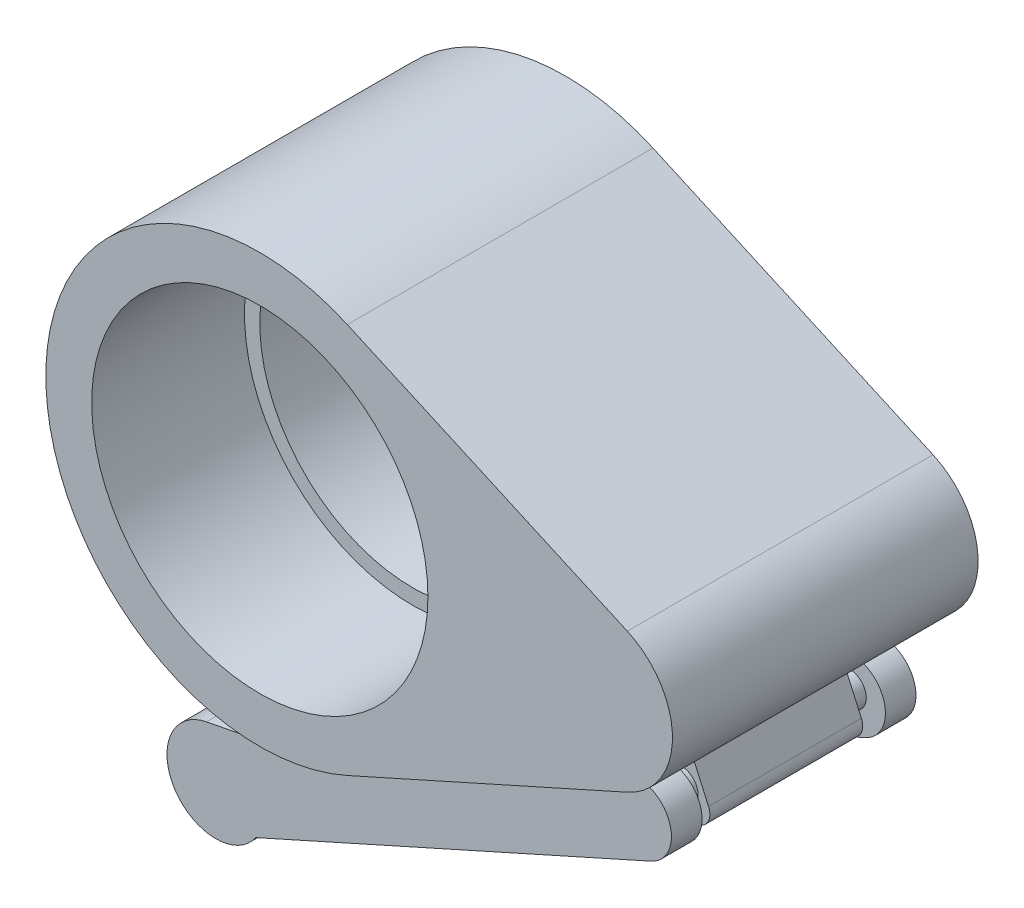
SolidWorks part; units mm, degrees
material "BUTYL"
ref_plane "Plan de face" through (0, 0, 0) normal (0, 0, 1) x (1, 0, 0)
ref_plane "Plan de dessus" through (0, 0, 0) normal (0, 1, 0) x (1, 0, 0)
ref_plane "Plan de droite" through (0, 0, 0) normal (1, 0, 0) x (0, 0, -1)
sketch "Esquisse2" plane through (0, 0, 0) normal (0, 0, 1) x (1, 0, 0)
  line L0 (5.7273, 12.7749) -> (24.0455, 4.5625)
  line L1 (5.7273, -12.7749) -> (24.0455, -4.5625)
  arc A0 (5.7273, 12.7749) -> (5.7273, -12.7749) centre (0, 0) ccw
  arc A1 (24.0455, -4.5625) -> (24.0455, 4.5625) centre (22, 0) ccw
  circle A2 centre (0, 0) radius 10
  dimension "D1" = 14
  dimension "D3" = 5
  dimension "D4" = 20
  dimension "D2" = 22
extrude "Boss.-Extru.1" add sketch "Esquisse2" along normal blind 20
sketch "Esquisse3" plane through (0, 0, 20) normal (0, 0, 1) x (1, 0, 0)
  circle A0 centre (0, 0) radius 11
  circle A1 centre (0, 0) radius 10
  dimension "D1" = 22
  dimension "D2" = 1
extrude "Enlèv. mat.-Extru.1" cut sketch "Esquisse3" against normal blind 10
sketch "Esquisse4" plane through (5.7273, -12.7749, 0) normal (0.4091, -0.9125, 0) x (0.9125, 0.4091, 0)
  line L0 (0, 20) -> (20.0749, 20) construction
  line L1 (16.0749, 15) -> (19.0749, 15)
  line L2 (16.0749, 15) -> (16.0749, 5)
  line L3 (16.0749, 5) -> (19.0749, 5)
  line L4 (19.0749, 15) -> (19.0749, 5)
  line L5 (20.0749, 20) -> (20.0749, 0) construction
  dimension "D1" = 10
  dimension "D2" = 5
  dimension "D3" = 1
  dimension "D4" = 3
extrude "Boss.-Extru.2" add sketch "Esquisse4" along normal blind 4
sketch "Esquisse5" plane through (0, 0, 15) normal (0, 0, 1) x (1, 0, 0)
  line L0 (24.7693, -8.6215) -> (23.133, -4.9716) construction
  line L1 (24.7693, -8.6215) -> (22.0318, -9.8488) construction
  circle A0 centre (22.5824, -7.4102) radius 1.1
  dimension "D3" = 2.2
  dimension "D1" = 1.5
  dimension "D2" = 2
extrude "Boss.-Extru.3" add sketch "Esquisse5" along normal blind 1
sketch "Esquisse6" plane through (7.3636, -16.4249, 0) normal (0.4091, -0.9125, 0) x (0.9125, 0.4091, 0)
  line L0 (16.0749, 10) -> (19.0749, 10) construction
  line L1 (16.0749, 15) -> (16.0749, 5) construction
  line L2 (19.0749, 5) -> (19.0749, 15) construction
ref_plane "Plan1" through (0, 0, 10) normal (0, 0, 1) x (1, 0, 0)
mirror "Symétrie1" about plane through (0, 0, 10) normal (0, 0, 1) of "Boss.-Extru.3"
sketch "Esquisse9" plane through (0, 0, 16) normal (0, 0, 1) x (1, 0, 0)
  line L0 (23.6051, -9.6914) -> (-2.2602, -21.2874)
  line L1 (5.7273, -12.7749) -> (24.0455, -4.5625) construction
  line L2 (-5.4847, -16.3395) -> (-0.9203, -15.4625)
  line L3 (1.2837, -14.767) -> (21.7642, -5.5852)
  line L4 (19.483, -6.6079) -> (21.3239, -10.7141)
  line L5 (22.0318, -9.8488) -> (20.3955, -6.1988) construction
  line L6 (22.5824, -7.4102) -> (23.6622, -9.8186) construction
  arc A0 (-2.2602, -21.2874) -> (-5.4847, -16.3395) centre (-4.8828, -19.4719) cw
  arc A1 (21.7642, -5.5852) -> (23.6051, -9.6914) centre (22.6847, -7.6383) cw
  arc A2 (1.2837, -14.767) -> (-0.9203, -15.4625) centre (-2.8072, -5.6421) cw
  circle M8 centre (22.5824, -7.4102) radius 1.1
  dimension "D1" = 10
  dimension "D2" = 4.5
  dimension "D3" = 30
  dimension "D4" = 1
extrude "Boss.-Extru.5" add sketch "Esquisse9" along normal blind 2 contours A1 L3 L4 L0 M8 | M8 region at (22.4333, -10.1332, 16) region at (22.5824, -7.4102, 16)
extrude "Boss.-Extru.6" add sketch "Esquisse9<4>" against normal up to surface (6 mm away) and the other way blind 2 contours L3 A2 L2 A0 L0 L4 region at (5.89, -15.0189, 16) up to plane "Plan1"
sketch "Esquisse9<4>" plane through (0, 0, 16) normal (0, 0, 1) x (1, 0, 0) same geometry as "Esquisse9"
mirror "Symétrie2" about plane through (0, 0, 10) normal (0, 0, 1) of "Boss.-Extru.5", "Boss.-Extru.6"
fillet "Congé1" radius 1 1 edges at (24.7693, -8.6215, 10)
fillet "Congé2" radius 1 1 edges at (22.0318, -9.8488, 10)
